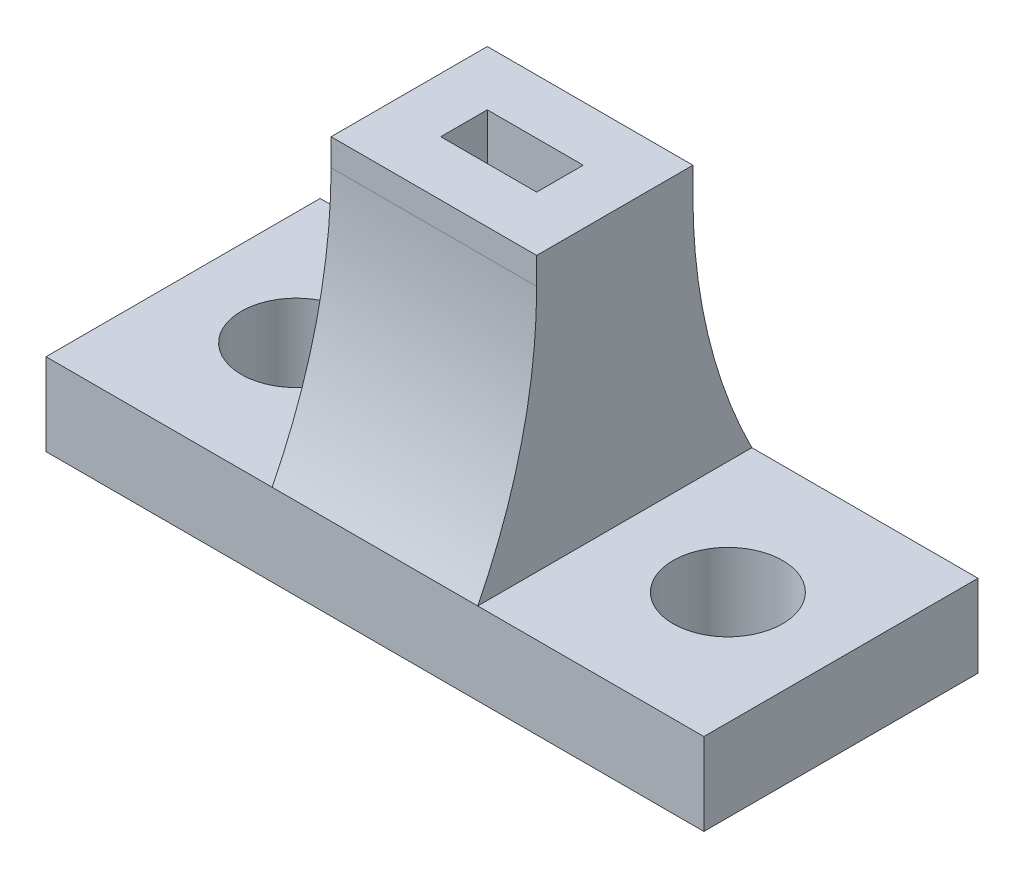
SolidWorks part; units mm, degrees
ref_plane "Front Plane" through (0, 0, 0) normal (0, 0, 1) x (1, 0, 0)
ref_plane "Top Plane" through (0, 0, 0) normal (0, 1, 0) x (1, 0, 0)
ref_plane "Right Plane" through (0, 0, 0) normal (1, 0, 0) x (0, 0, -1)
sketch "Sketch1" plane through (0, 0, 0) normal (0, 1, 0) x (1, 0, 0)
  line L1 (-1.75, 0.85) -> (1.75, 0.85)
  line L2 (-1.75, 0.85) -> (-1.75, -0.85)
  line L3 (-1.75, -0.85) -> (1.75, -0.85)
  line L4 (1.75, 0.85) -> (1.75, -0.85)
  line L5 (-1.75, 0.85) -> (1.75, -0.85) construction
  line L6 (-1.75, -0.85) -> (1.75, 0.85) construction
  line L7 (-3.75, 2.85) -> (3.75, 2.85)
  line L8 (-3.75, 2.85) -> (-3.75, -2.85)
  line L9 (-3.75, -2.85) -> (3.75, -2.85)
  line L10 (3.75, 2.85) -> (3.75, -2.85)
  line L11 (-3.75, 2.85) -> (3.75, -2.85) construction
  line L12 (-3.75, -2.85) -> (3.75, 2.85) construction
  point P0 (0, 0)
  point P6 (0, 0)
  dimension "D1" = 1.7
  dimension "D2" = 3.5
  dimension "D3" = 2
  dimension "D4" = 2
extrude "Boss-Extrude1" add sketch "Sketch1" along normal blind 10
sketch "Sketch2" plane through (0, 0, 0) normal (0, -1, 0) x (1, 0, 0)
  line L1 (-12, 5) -> (12, 5)
  line L2 (-12, 5) -> (-12, -5)
  line L3 (-12, -5) -> (12, -5)
  line L4 (12, 5) -> (12, -5)
  line L5 (-12, 5) -> (12, -5) construction
  line L6 (-12, -5) -> (12, 5) construction
  point P0 (0, 0)
  dimension "D1" = 10
  dimension "D2" = 24
extrude "Boss-Extrude2" add sketch "Sketch2" along normal blind 3
fillet "Fillet1" radius 20 2 edges at (0, 0, -2.85) (0, 0, 2.85)
sketch "Sketch3" plane through (0, 0, 0) normal (0, 1, 0) x (1, 0, 0)
  line L0 (-7.875, 5) -> (-7.875, -5) construction
  line L1 (-12, 5) -> (-3.75, 5) construction
  line L2 (-3.75, -5) -> (-12, -5) construction
  line L3 (7.875, 5) -> (7.875, -5) construction
  line L4 (3.75, 5) -> (12, 5) construction
  line L5 (12, -5) -> (3.75, -5) construction
  circle A0 centre (-7.875, 0) radius 2
  circle A1 centre (7.875, 0) radius 2
  dimension "D1" = 4
  dimension "D2" = 4
extrude "Cut-Extrude1" cut sketch "Sketch3" against normal blind 3
